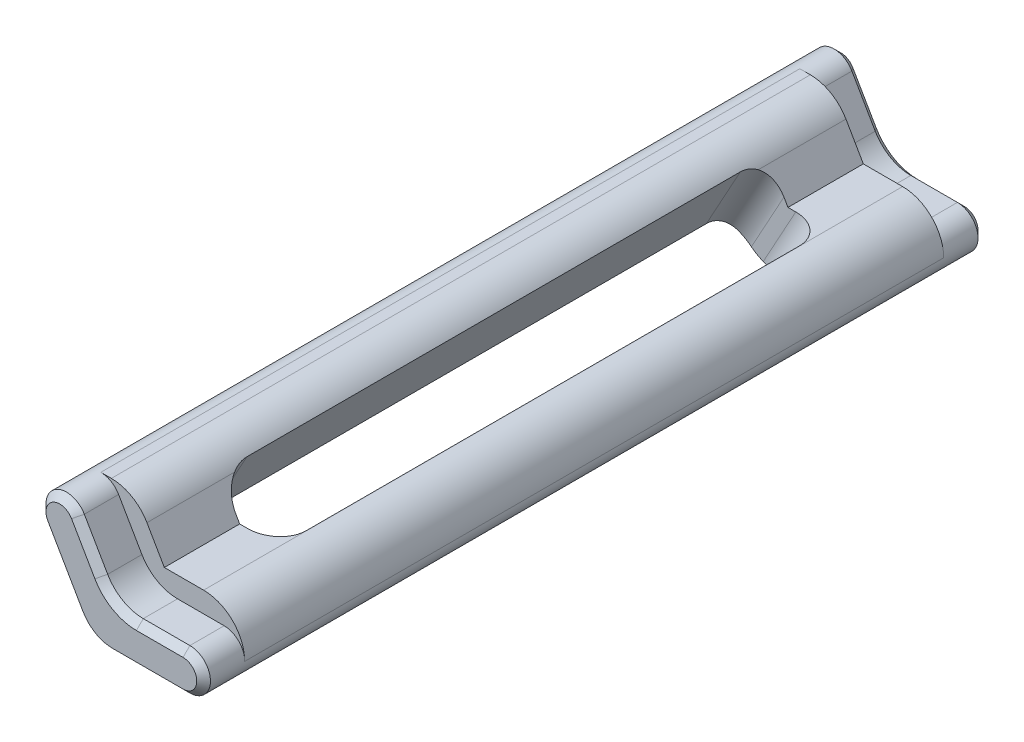
SolidWorks part; units mm, degrees
material "PLA"
ref_plane "前视基准面" through (0, 0, 0) normal (0, 0, 1) x (1, 0, 0)
ref_plane "上视基准面" through (0, 0, 0) normal (0, 1, 0) x (1, 0, 0)
ref_plane "右视基准面" through (0, 0, 0) normal (1, 0, 0) x (0, 0, -1)
sketch "草图1" plane through (0, 0, 0) normal (0, 0, 1) x (1, 0, 0)
  line L0 (0, 0) -> (6, 0)
  line L1 (0, 0) -> (-3, 5.1962)
  line L2 (0.866, 1.5) -> (6, 1.5)
  line L3 (0.866, 1.5) -> (-1.701, 5.9462)
  line L4 (-0.866, -1.5) -> (6, -1.5)
  line L5 (-0.866, -1.5) -> (-4.299, 4.4462)
  circle A0 centre (-3, 5.1962) radius 1.5
  circle A1 centre (6, 0) radius 1.5
  dimension "D1" = 6
  dimension "D2" = 6
  dimension "D3" = 120
  dimension "D4" = 1.5
  dimension "D5" = 1.5
extrude "凸台-拉伸1" add sketch "草图1" along normal blind 3 contours A0 | A1 L2 L3 A0 L1 L0 | A1 L0 L1 A0 L5 L4 | A1 region at (-1.0369, 1.9994, 0) region at (2.25, -0.1189, 0) region at (4.9693, 1.0307, 0) region at (-3.3772, 3.7882, 0)
sketch "草图2" plane through (0, 0, 3) normal (0, 0, 1) x (1, 0, 0)
  line L0 (-0.866, -1.5) -> (-4.299, 4.4462)
  line L1 (-3, 6.6962) -> (-0.5, 6.6962)
  line L2 (-0.5, 6.6962) -> (1.634, 3)
  line L3 (1.634, 3) -> (7.5, 3)
  line L4 (7.5, 3) -> (7.5, 0)
  line L5 (0.866, 1.5) -> (-1.701, 5.9462) construction
  line L6 (0.866, 1.5) -> (6, 1.5) construction
  circle A0 centre (-3, 5.1962) radius 1.5
  arc A1 (6, -1.5) -> (6, 1.5) centre (6, 0) ccw construction
  line M5 (-0.866, -1.5) -> (6, -1.5)
  arc M6 (6, -1.5) -> (6, 1.5) centre (6, 0) ccw
  line M7 (6, 1.5) -> (0.866, 1.5)
  line M8 (0.866, 1.5) -> (-1.701, 5.9462)
  arc M9 (-1.701, 5.9462) -> (-4.299, 4.4462) centre (-3, 5.1962) ccw
  line M10 (-4.299, 4.4462) -> (-0.866, -1.5)
  dimension "D1" = 2.5
  dimension "D2" = 3
extrude "凸台-拉伸2" add sketch "草图2" along normal blind 51 contours L4 L3 L2 L1 M9 M8 M7 M6 | A0 M10 M5 M6 M7 M8 | A0 M9 region at (1.6284, 0.7799, 3) region at (-3, 5.1962, 3) region at (-1.75, 6.5716, 3)
sketch "草图3" plane through (0, 0, 54) normal (0, 0, 1) x (1, 0, 0)
  line L0 (0, 0) -> (6, 0)
  line L1 (0, 0) -> (-3, 5.1962)
  line L2 (-0.866, -1.5) -> (6, -1.5) construction
  line L3 (-4.299, 4.4462) -> (-0.866, -1.5) construction
  line L4 (0.866, 1.5) -> (6, 1.5)
  line L5 (0.866, 1.5) -> (-1.701, 5.9462)
  line L6 (-0.866, -1.5) -> (6, -1.5)
  line L7 (-0.866, -1.5) -> (-4.299, 4.4462)
  circle A0 centre (-3, 5.1962) radius 1.5
  circle A1 centre (6, 0) radius 1.5
  arc M4 (-3, 6.6962) -> (-4.299, 4.4462) centre (-3, 5.1962) ccw
  line M5 (-4.299, 4.4462) -> (-0.866, -1.5)
  line M6 (-0.866, -1.5) -> (6, -1.5)
  arc M7 (6, -1.5) -> (7.5, 0) centre (6, 0) ccw
  dimension "D1" = 6
  dimension "D2" = 6
  dimension "D3" = 1.5
  dimension "D4" = 1.5
extrude "凸台-拉伸3" add sketch "草图3" along normal blind 3 contours A0 M4 | A1 L4 L5 A0 L1 L0 | A1 L0 L1 A0 M5 M6 | A1 M7 region at (-1.0369, 1.9994, 54) region at (2.25, -0.1189, 54) region at (4.9693, 1.0307, 54) region at (-3.3772, 3.7882, 54)
fillet "圆角1" radius 3 5 edges at (0.866, 1.5, 55.5) (7.5, 3, 28.5) (-0.5, 6.6962, 28.5) (0.866, 1.5, 1.5) (-0.866, -1.5, 28.5)
chamfer "倒角1" distance 0.5 16 edges at (7.5, 0, 0) (4.299, 1.5, 0) (1.0981, 1.9019, 0) (-0.8505, 4.4731, 0) (-3.75, 6.4952, 0) (-3.0155, 2.2231, 0) (-0.634, -1.0981, 0) (3.433, -1.5, 0) (3.433, -1.5, 57) (7.5, 0, 57) (-0.634, -1.0981, 57) (4.299, 1.5, 57) (-3.0155, 2.2231, 57) (1.0981, 1.9019, 57) (-3.75, 6.4952, 57) (-0.8505, 4.4731, 57)
ref_plane "基准面1" through (2.4861, 4.5281, 0) normal (0.4813, 0.8766, 0) x (0.8766, -0.4813, 0)
sketch "草图4" plane through (2.4861, 4.5281, 0) normal (0.4813, 0.8766, 0) x (0.8766, -0.4813, 0)
  line L0 (-0.0115, -54) -> (-0.0115, -3) construction
  line L1 (2.4885, -48.5) -> (-2.5115, -48.5)
  line L2 (2.4885, -48.5) -> (2.4885, -8.5)
  line L3 (2.4885, -8.5) -> (-2.5115, -8.5)
  line L4 (-2.5115, -48.5) -> (-2.5115, -8.5)
  line L5 (2.4885, -48.5) -> (-2.5115, -8.5) construction
  line L6 (2.4885, -8.5) -> (-2.5115, -48.5) construction
  point P0 (-0.0115, -28.5)
  dimension "D1" = 40
  dimension "D2" = 5
extrude "切除-拉伸1" cut sketch "草图4" against normal through all
fillet "圆角2" radius 2 4 edges at (-1.0769, 3.257, 48.5) (3.2507, 0.75, 48.5) (-1.0769, 3.257, 8.5) (3.2507, 0.75, 8.5)
